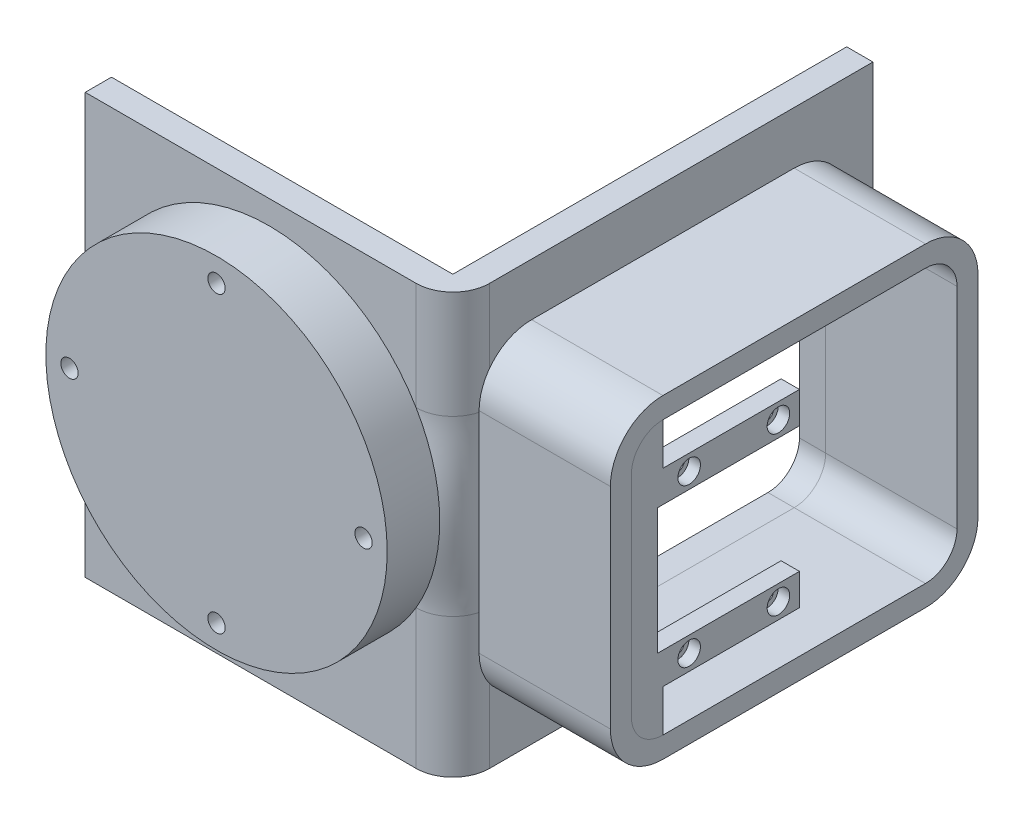
SolidWorks part; units mm, degrees
ref_plane "Front Plane" through (0, 0, 0) normal (0, 0, 1) x (1, 0, 0)
ref_plane "Top Plane" through (0, 0, 0) normal (0, 1, 0) x (1, 0, 0)
ref_plane "Right Plane" through (0, 0, 0) normal (1, 0, 0) x (0, 0, -1)
sketch "Sketch1" plane through (0, 0, 0) normal (0, 0, 1) x (1, 0, 0)
  circle A5 centre (0, 0) radius 32.5
  dimension "D1" = 65
extrude "Boss-Extrude1" add sketch "Sketch1" against normal blind 10
ref_plane "Plane1" through (60, 0, 0) normal (1, 0, 0) x (0, 0, -1)
ref_plane "Plane2" through (60, 0, 0) normal (1, 0, 0) x (0, 0, -1)
sketch "Sketch10" plane through (0, 0, -10) normal (0, 0, -1) x (-1, 0, 0)
  line L0 (0, -3) -> (0, 0) construction
  line L1 (-35, -43) -> (35, -43)
  line L2 (-35, -43) -> (-35, 37)
  line L3 (-35, 37) -> (35, 37)
  line L4 (35, -43) -> (35, 37)
  line L5 (-35, -43) -> (35, 37) construction
  line L6 (-35, 37) -> (35, -43) construction
  point P0 (0, -3)
  dimension "D3" = 3
  dimension "D1" = 80
  dimension "D2" = 70
extrude "Boss-Extrude6" add sketch "Sketch10" along normal blind 80
sketch "Sketch2" plane through (60, 0, 0) normal (1, 0, 0) x (0, 0, -1)
  line L2 (0, -3) -> (146.6861, -3) construction
  line L3 (50, -3) -> (50, 30) construction
  line L5 (10, 37) -> (10, -43) construction
  line L6 (90, 37) -> (90, -43) construction
  line L7 (25, -33) -> (75, -33)
  line L8 (15, -23) -> (15, 17)
  line L9 (25, 27) -> (75, 27)
  line L10 (85, -23) -> (85, 17)
  line L11 (15, -33) -> (85, 27) construction
  line L12 (15, 27) -> (85, -33) construction
  arc A1 (25, -33) -> (15, -23) centre (25, -23) cw
  arc A2 (75, -33) -> (85, -23) centre (75, -23) ccw
  arc A3 (75, 27) -> (85, 17) centre (75, 17) cw
  arc A4 (15, 17) -> (25, 27) centre (25, 17) cw
  point P0 (90, -3)
  dimension "D1" = 70
  dimension "D3" = 10
  dimension "D2" = 60
extrude "Boss-Extrude2" add sketch "Sketch2" against normal up to surface (25 mm away) separate body up to face at (35, -3, -50)
sketch "Sketch11" plane through (0, 37, 0) normal (0, 1, 0) x (1, 0, 0)
  line L1 (-35, 90) -> (30, 90)
  line L2 (-35, 90) -> (-35, 15)
  line L3 (-35, 15) -> (30, 15)
  line L4 (30, 90) -> (30, 15)
  dimension "D1" = 75
  dimension "D2" = 65
extrude "Cut-Extrude5" cut sketch "Sketch11" against normal through all
sketch "Sketch4" plane through (35, 0, 0) normal (-1, 0, 0) x (0, 0, 1)
  line L8 (-75, -29) -> (-25, -29)
  line L9 (-81, 17) -> (-81, -23)
  line L10 (-25, 23) -> (-75, 23)
  line L11 (-19, -23) -> (-19, 17)
  line L12 (-75, -29) -> (-25, -29)
  line L13 (-81, 17) -> (-81, -23)
  line L14 (-25, 23) -> (-75, 23)
  line L15 (-19, -23) -> (-19, 17)
  arc A10 (-81, -23) -> (-75, -29) centre (-75, -23) ccw
  arc A11 (-75, 23) -> (-81, 17) centre (-75, 17) ccw
  arc A12 (-19, 17) -> (-25, 23) centre (-25, 17) ccw
  arc A13 (-25, -29) -> (-19, -23) centre (-25, -23) ccw
  arc A14 (-81, -23) -> (-75, -29) centre (-75, -23) ccw
  arc A15 (-75, 23) -> (-81, 17) centre (-75, 17) ccw
  arc A16 (-19, 17) -> (-25, 23) centre (-25, 17) ccw
  arc A17 (-25, -29) -> (-19, -23) centre (-25, -23) ccw
  dimension "D1" = 4
extrude "Cut-Extrude2" cut sketch "Sketch4" against normal through all contours L12 A17 L15 A16 L14 A15 L13 A14 region at (35, -3, -50)
sketch "Sketch5" plane through (60, 0, 0) normal (1, 0, 0) x (0, 0, -1)
  line L0 (54, -3) -> (19, -3) construction
  line L1 (51, 15) -> (51, 9)
  line L2 (51, 9) -> (24, 9)
  line L3 (24, 9) -> (24, -15)
  line L4 (24, -15) -> (51, -15)
  line L5 (51, -15) -> (51, -21)
  line L6 (51, -21) -> (25, -21)
  line L8 (51, 15) -> (25, 15)
  line L10 (54, -3) -> (54, -18) construction
  line L11 (54, -18) -> (47, -18) construction
  line L12 (47, -18) -> (39, -18) construction
  line L13 (39, -18) -> (30, -18) construction
  line L15 (19, 17) -> (19, -23)
  line L16 (25, 15) -> (25, 23)
  line L17 (25, -21) -> (25, -29)
  line L18 (19, -23) -> (19, 17) construction
  circle A0 centre (54, -3) radius 11 construction
  arc A1 (25, 23) -> (19, 17) centre (25, 17) ccw construction
  circle A2 centre (47, -18) radius 1.25
  arc A3 (25, 23) -> (19, 17) centre (25, 17) ccw
  circle A6 centre (30, -18) radius 1.25
  circle A7 centre (47, 12) radius 1.25
  circle A9 centre (30, 12) radius 1.25
  arc A10 (19, -23) -> (25, -29) centre (25, -23) ccw
  point P8 (24, -3)
  dimension "D1" = 22
  dimension "D6" = 2.5
  dimension "D3" = 24
  dimension "D4" = 15
  dimension "D5" = 7
  dimension "D7" = 17
  dimension "D9" = 6
  dimension "D10" = 5
  dimension "D12" = 3
  dimension "D2" = 30
extrude "Boss-Extrude3" add sketch "Sketch5" against normal blind 3.5
sketch "Sketch13" plane through (35, 0, 0) normal (1, 0, 0) x (0, 0, -1)
  line L4 (19, 17) -> (19, -23)
  line L5 (25, -29) -> (75, -29)
  line L6 (81, -23) -> (81, 17)
  line L7 (75, 23) -> (25, 23)
  line L8 (19, 17) -> (19, -23)
  line L9 (25, -29) -> (75, -29)
  line L10 (81, -23) -> (81, 17)
  line L11 (75, 23) -> (25, 23)
  arc A6 (25, 23) -> (19, 17) centre (25, 17) ccw
  arc A7 (19, -23) -> (25, -29) centre (25, -23) ccw
  arc A8 (75, -29) -> (81, -23) centre (75, -23) ccw
  arc A9 (81, 17) -> (75, 23) centre (75, 17) ccw
  arc A10 (25, 23) -> (19, 17) centre (25, 17) ccw
  arc A11 (19, -23) -> (25, -29) centre (25, -23) ccw
  arc A12 (75, -29) -> (81, -23) centre (75, -23) ccw
  arc A13 (81, 17) -> (75, 23) centre (75, 17) ccw
  dimension "D1" = 0
extrude "Cut-Extrude6" cut sketch "Sketch13" against normal up to surface (5 mm away) up to face at (30, -3, -52.5)
sketch "Sketch14" plane through (0, 0, 0) normal (0, 0, 1) x (1, 0, 0)
  circle A2 centre (0, 0) radius 28.5
  circle A3 centre (0, 0) radius 28.5
  dimension "D1" = 4
sketch "Sketch16" plane through (60, 0, 0) normal (1, 0, 0) x (0, 0, -1)
  circle A0 centre (47, -18) radius 2.15
  circle A2 centre (30, -18) radius 2.15
  circle A3 centre (30, 12) radius 2.15
  circle A5 centre (47, 12) radius 2.15
  point P3 (30, 10.5)
  dimension "D1" = 4.3
extrude "Cut-Extrude8" cut sketch "Sketch16" against normal blind 2.2
fillet "Fillet1" radius 7 1 edges at (35, -3, -10)
fillet "Fillet2" [suppressed] radius 10
sketch "Sketch17" plane through (0, 0, -15) normal (0, 0, -1) x (-1, 0, 0)
  line L0 (-28, 0) -> (0, 0) construction
  line L1 (0, 28) -> (0, 0) construction
  line L2 (28, 0) -> (0, 0) construction
  line L3 (0, -28) -> (0, 0) construction
  circle A0 centre (-28, 0) radius 1.65
  circle A1 centre (0, 28) radius 1.65
  circle A2 centre (28, 0) radius 1.65
  circle A3 centre (0, -28) radius 1.65
  point P2 (0, 0)
  point P10 (0, 0)
  point P17 (0, 0)
  dimension "D4" = 3.3
  dimension "D3" = 28
  dimension "D1" = 4
  dimension "D2" = 4
extrude "Cut-Extrude9" cut sketch "Sketch17" against normal through all
